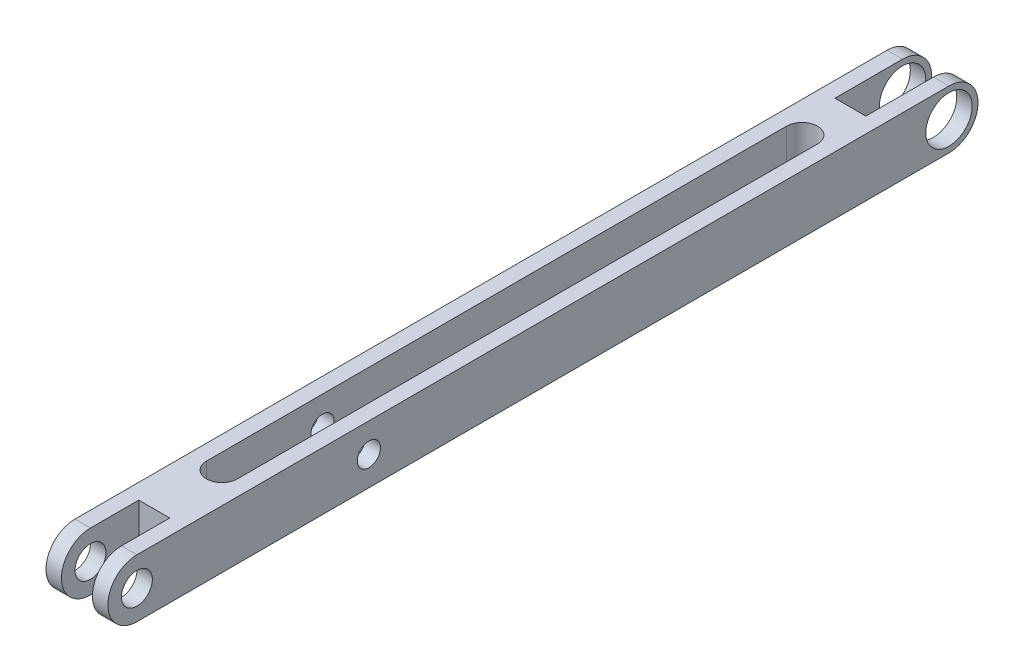
SolidWorks part; units mm, degrees
material "ABS"
ref_plane "前视基准面" through (0, 0, 0) normal (0, 0, 1) x (1, 0, 0)
ref_plane "上视基准面" through (0, 0, 0) normal (0, 1, 0) x (1, 0, 0)
ref_plane "右视基准面" through (0, 0, 0) normal (1, 0, 0) x (0, 0, -1)
sketch "草图2" plane through (0, 0, 0) normal (1, 0, 0) x (0, 0, -1)
  line L0 (-105, 7.5) -> (-105, -7.5) construction
  line L1 (-105, -7.5) -> (105, -7.5)
  line L3 (-105, 7.5) -> (105, 7.5)
  line L5 (-105, -7.5) -> (105, 7.5) construction
  line L6 (-105, 7.5) -> (105, -7.5) construction
  line L7 (105, 7.5) -> (105, -7.5) construction
  arc A0 (-105, 7.5) -> (-105, -7.5) centre (-105, 0) ccw
  arc A1 (105, 7.5) -> (105, -7.5) centre (105, 0) cw
  point P0 (0, 0)
  dimension "D1" = 15
  dimension "D2" = 210
extrude "凸台-拉伸1" add sketch "草图2" along normal blind 16
sketch "草图3" plane through (0, 7.5, 0) normal (0, 1, 0) x (1, 0, 0)
  line L1 (4, -112.5) -> (4, -92.5)
  line L2 (0, -112.5) -> (16, -112.5) construction
  line L3 (4, -92.5) -> (12, -92.5)
  line L4 (12, -92.5) -> (12, -112.5)
  line L5 (12, -112.5) -> (4, -112.5)
  line L6 (0, 105) -> (0, -105) construction
  line L7 (16, 105) -> (16, -105) construction
  line L10 (4, 112.5) -> (12, 112.5)
  line L14 (4, 112.5) -> (4, 87.5)
  line L15 (4, 87.5) -> (12, 87.5)
  line L16 (12, 87.5) -> (12, 112.5)
  line L17 (16, 105) -> (0, 105) construction
  dimension "D1" = 4
  dimension "D2" = 4
  dimension "D3" = 20
  dimension "D4" = 8
  dimension "D5" = 25
  dimension "D6" = 7.5
  dimension "D7" = 4
extrude "切除-拉伸1" cut sketch "草图3" against normal through all
sketch "草图4" plane through (16, 0, 0) normal (1, 0, 0) x (0, 0, -1)
  circle A0 centre (-105, 0) radius 4
  circle A1 centre (105, 0) radius 6
  dimension "D1" = 8
  dimension "D2" = 12
extrude "切除-拉伸2" cut sketch "草图4" against normal through all
sketch "草图5" plane through (0, -7.5, 0) normal (0, -1, 0) x (1, 0, 0)
  line L0 (8, 75) -> (8, -75) construction
  line L1 (12, 75) -> (12, -75)
  line L2 (4, 75) -> (4, -75)
  line L3 (0, 0) -> (8, 0) construction
  line L4 (0, 105) -> (0, -105) construction
  arc A0 (12, 75) -> (4, 75) centre (8, 75) ccw
  arc A1 (4, -75) -> (12, -75) centre (8, -75) ccw
  point P2 (8, 0)
  dimension "D1" = 8
  dimension "D2" = 8
  dimension "D3" = 150
extrude "切除-拉伸3" cut sketch "草图5" against normal through all
sketch "草图6" plane through (0, 0, 0) normal (-1, 0, 0) x (0, 0, 1)
  line L0 (45, 0) -> (0, 0) construction
  circle A1 centre (45, 0) radius 3
  circle A3 centre (105, 0) radius 4 construction
  dimension "D1" = 60
  dimension "D2" = 6
extrude "切除-拉伸4" cut sketch "草图6" against normal through all
